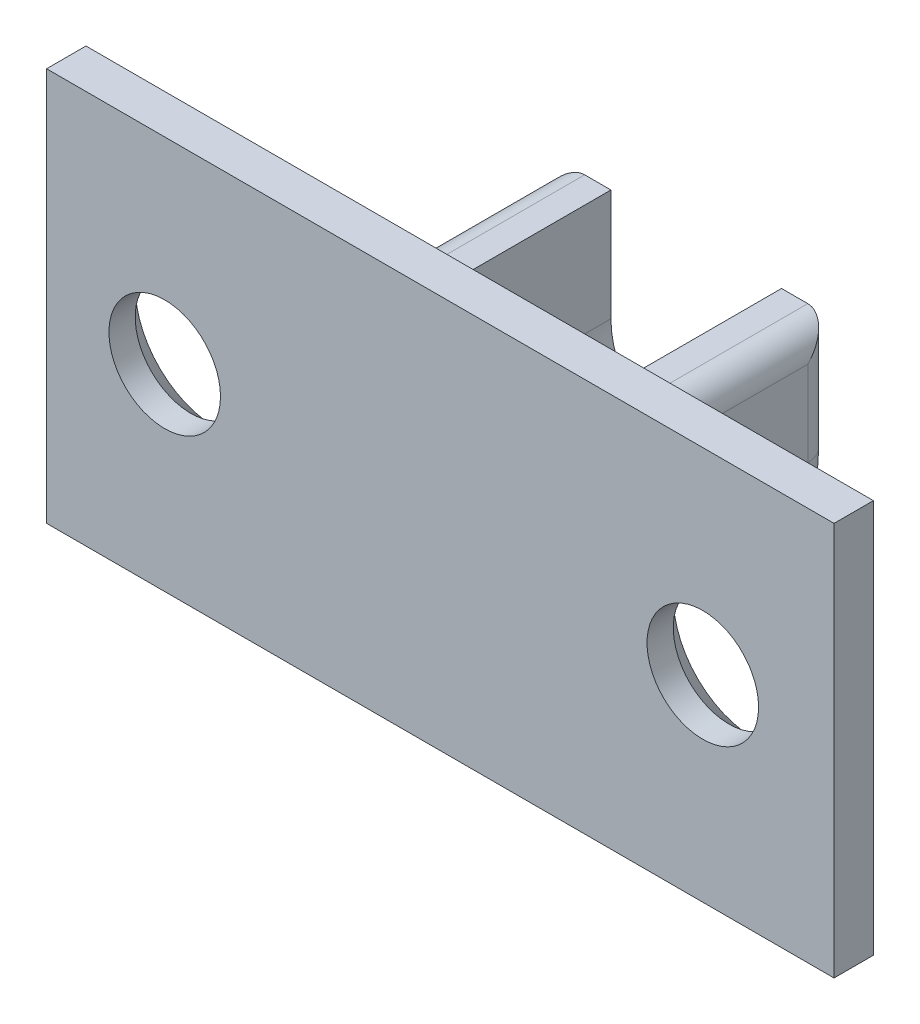
SolidWorks part; units mm, degrees
ref_plane "Plan de face" through (0, 0, 0) normal (0, 0, 1) x (1, 0, 0)
ref_plane "Plan de dessus" through (0, 0, 0) normal (0, 1, 0) x (1, 0, 0)
ref_plane "Plan de droite" through (0, 0, 0) normal (1, 0, 0) x (0, 0, -1)
sketch "Esquisse1" plane through (0, 0, 0) normal (0, 0, 1) x (1, 0, 0)
  line L0 (15.25, -991.781) -> (15.25, 49008.219) construction
  line L1 (0, 0) -> (30.5, 0)
  line L2 (0, 0) -> (0, 15)
  line L3 (0, 15) -> (30.5, 15)
  line L4 (30.5, 0) -> (30.5, 15)
  line L5 (-1000, 7.5) -> (49000, 7.5) construction
  line L6 (18.5, 7.5) -> (20.5, 7.5) construction
  line L7 (12, 7.5) -> (10, 7.5) construction
  line L8 (12, 7.5) -> (12, 11.75)
  line L9 (12, 11.75) -> (10, 11.75)
  line L10 (10, 7.5) -> (10, 11.75)
  line L11 (20.5, 7.5) -> (20.5, 11.75)
  line L12 (18.5, 11.75) -> (20.5, 11.75)
  line L13 (18.5, 7.5) -> (18.5, 11.75)
  circle A0 centre (5, 7.5) radius 2.125
  arc A1 (12, 7.5) -> (18.5, 7.5) centre (15.25, 7.5) ccw
  arc A2 (10, 7.5) -> (20.5, 7.5) centre (15.25, 7.5) ccw
  circle A3 centre (25.5, 7.5) radius 2.125
  point P10 (15.25, 15)
  point P12 (15.25, 7.5)
  point P18 (0, 7.5)
  dimension "D1" = 4.25
  dimension "D2" = 3.25
  dimension "D3" = 5.25
  dimension "D4" = 15
  dimension "D6" = 4.25
  dimension "D7" = 5
  dimension "D8" = 10
extrude "Boss.-Extru.3" add sketch "Esquisse1" along normal blind 2 contours L1 L4 L3 L2 A0 L11 L10 L9 L8 L13 L12 | L11 L12 L13 L8 L9 L10 region at (15.25, 7.5972, 0) region at (15.25, 4.1084, 0)
extrude "Boss.-Extru.4" add sketch "Esquisse1<5>" against normal blind 8 contours L11 L12 L13 L8 L9 L10 region at (15.25, 4.1084, 0)
sketch "Esquisse1<5>" plane through (0, 0, 0) normal (0, 0, 1) x (1, 0, 0) same geometry as "Esquisse1"
fillet "Congé3" radius 1 10 edges at (20.5, 9.625, -8) (10, 9.625, -8) (20.5, 9.625, 0) (20.5, 11.75, -4) (10, 11.75, -4) (11, 11.75, 0) (19.5, 11.75, 0) (10, 9.625, 0) (15.25, 2.25, 0) (15.25, 2.25, -8)
chamfer "Chanfrein2" distance 1 angle 45 2 edges at (7.125, 7.5, 0) (27.625, 7.5, 0)
chamfer "Chanfrein3" distance 0.5 angle 45 7 edges at (0, 15, 1) (0, 7.5, 2) (0, 0, 1) (0, 7.5, 0) (15.25, 15, 0) (30.5, 7.5, 0) (15.25, 0, 0)
